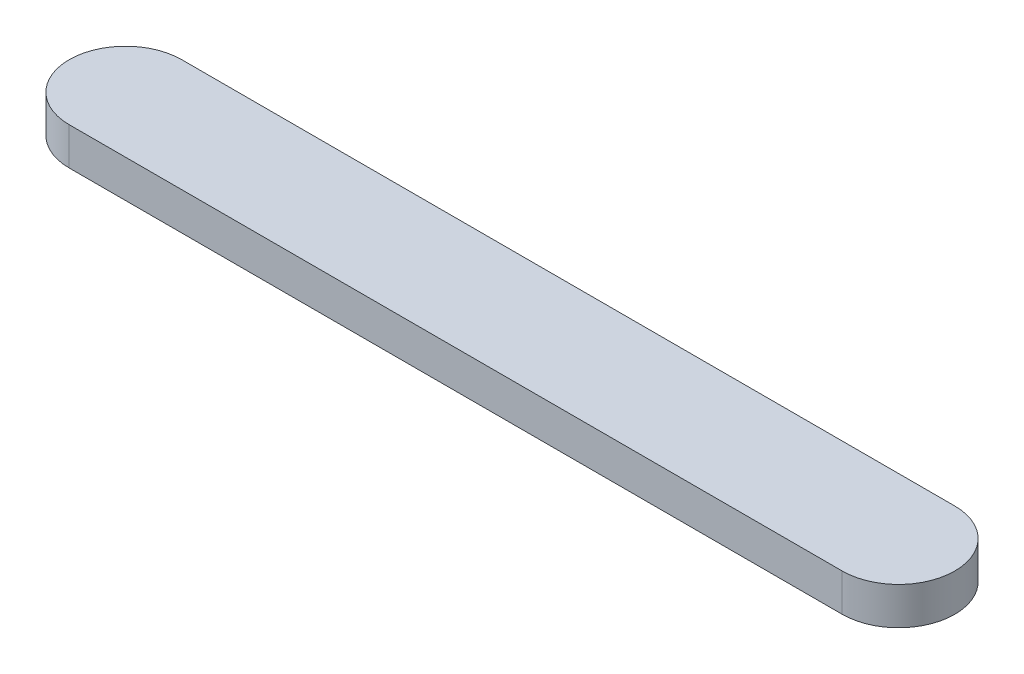
SolidWorks part; units mm, degrees
ref_plane "Plan de face" through (0, 0, 0) normal (0, 0, 1) x (1, 0, 0)
ref_plane "Plan de dessus" through (0, 0, 0) normal (0, 1, 0) x (1, 0, 0)
ref_plane "Plan de droite" through (0, 0, 0) normal (1, 0, 0) x (0, 0, -1)
sketch "Esquisse1" plane through (0, 0, 0) normal (0, 1, 0) x (1, 0, 0)
  line L0 (-103, -15) -> (103, -15)
  line L1 (-103, -15) -> (-103, 15) construction
  line L2 (103, -15) -> (103, 15) construction
  line L3 (-103, 15) -> (103, 15)
  line L4 (-103, -15) -> (103, 15) construction
  line L5 (103, -15) -> (-103, 15) construction
  arc A0 (103, 15) -> (103, -15) centre (103, 0) cw
  arc A1 (-103, 15) -> (-103, -15) centre (-103, 0) ccw
  point P1 (0, 0)
  point P3 (0, 0)
  point P9 (103, -15)
  point P10 (103, 15)
  dimension "D1" = 103
  dimension "D2" = 30
extrude "Boss.-Extru.1" add sketch "Esquisse1" along normal blind 10
